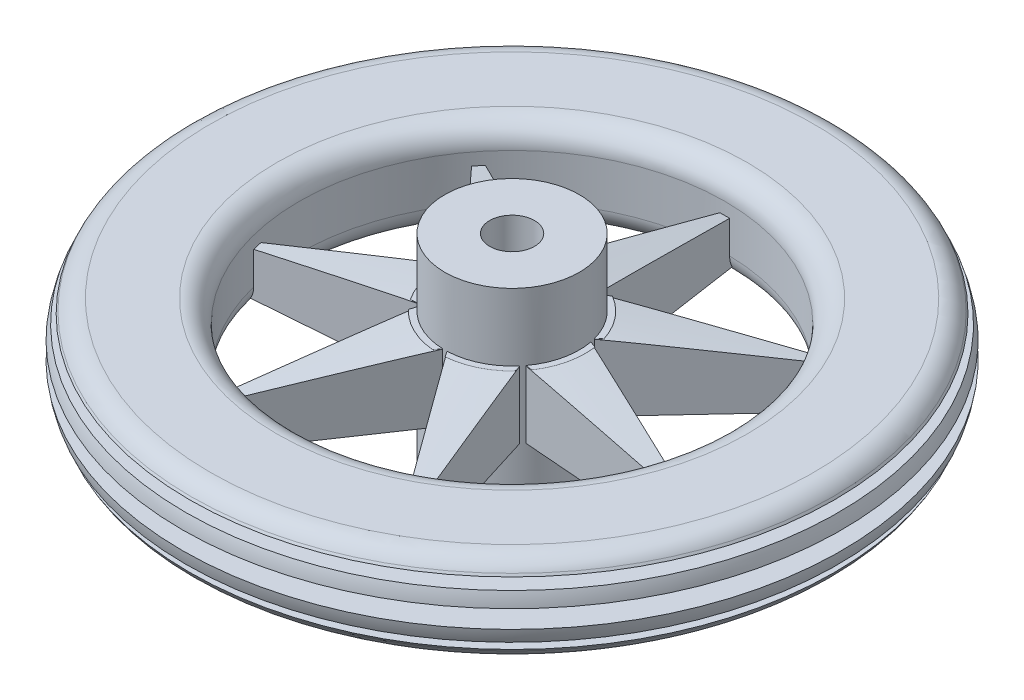
SolidWorks part; units mm, degrees
ref_plane "Front Plane" through (0, 0, 0) normal (0, 0, 1) x (1, 0, 0)
ref_plane "Top Plane" through (0, 0, 0) normal (0, 1, 0) x (1, 0, 0)
ref_plane "Right Plane" through (0, 0, 0) normal (1, 0, 0) x (0, 0, -1)
sketch "Sketch1" plane through (0, 0, 0) normal (0, 1, 0) x (1, 0, 0)
  circle A0 centre (0, 0) radius 50
  dimension "D1" = 100
sketch "Sketch2" plane through (0, 0, 0) normal (1, 0, 0) x (0, 0, -1)
  line L0 (50, 0) -> (-50, 0) construction
  line L1 (-58.6107, 0) -> (-80.5773, 0) construction
  line L2 (-69.791, 10) -> (-47.4303, 10)
  line L3 (-69.791, -10) -> (-47.4303, -10)
  line L4 (-47.4303, 10) -> (-47.4303, -10)
  line L5 (-73.4767, 2) -> (-59.6667, 2)
  line L6 (-59.6667, 2) -> (-59.6667, -2)
  line L7 (-59.6667, -2) -> (-73.4767, -2)
  line L8 (-71.8772, -7) -> (-59.6667, -7)
  line L9 (-59.6667, -7) -> (-59.6667, -5)
  line L10 (-59.6667, -5) -> (-72.7528, -5)
  line L11 (-59.6667, 7) -> (-59.6667, 5)
  line L12 (-59.6667, 5) -> (-72.7528, 5)
  line L13 (-71.8772, 7) -> (-59.6667, 7)
  line L14 (-58.6107, 0) -> (-58.6107, 15.4719) construction
  arc A0 (-69.791, 10) -> (-71.8772, 7) centre (-58.6107, 0) ccw
  arc A2 (-72.7528, 5) -> (-73.4767, 2) centre (-58.6107, 0) ccw
  arc A3 (-73.4767, -2) -> (-72.7528, -5) centre (-58.6107, 0) ccw
  arc A4 (-71.8772, -7) -> (-69.791, -10) centre (-58.6107, 0) ccw
  dimension "D1" = 30
  dimension "D2" = 10
  dimension "D3" = 10
  dimension "D4" = 4
  dimension "D5" = 2
  dimension "D6" = 2
  dimension "D7" = 5
  dimension "D8" = 20
sweep "Sweep1" add profiles "Sketch2" path "Sketch1"
sketch "Sketch3" plane through (0, 0, 0) normal (0, 1, 0) x (1, 0, 0)
  line L0 (37.7487, 28.7171) -> (14.507, 3.814)
  line L1 (6.9465, 13.2946) -> (36.397, 30.4121)
  line L2 (45.9879, -11.6083) -> (12.0269, -8.9641)
  line L3 (-6.0631, 13.72) -> (-1.084, 47.4179)
  line L4 (1.084, 47.4179) -> (6.0631, 13.72)
  line L5 (14.7252, 2.8581) -> (46.4703, -9.4947)
  line L6 (19.5973, -43.1924) -> (0.4902, -14.992)
  line L7 (11.4156, -9.7306) -> (21.5505, -42.2518)
  line L8 (-21.5505, -42.2518) -> (-11.4156, -9.7306)
  line L9 (-0.4902, -14.992) -> (-19.5973, -43.1924)
  line L10 (-46.4703, -9.4947) -> (-14.7252, 2.8581)
  line L11 (-12.0269, -8.9641) -> (-45.9879, -11.6083)
  line L12 (-36.397, 30.4121) -> (-6.9465, 13.2946)
  line L13 (-14.507, 3.814) -> (-37.7487, 28.7171)
  circle A0 centre (0, 0) radius 47.4303 construction
  arc A1 (1.084, 47.4179) -> (-1.084, 47.4179) centre (0, 0) ccw
  circle A2 centre (0, 0) radius 15
  arc A5 (37.7487, 28.7171) -> (36.397, 30.4121) centre (0, 0) ccw
  circle A6 centre (0, 0) radius 15
  arc A7 (45.9879, -11.6083) -> (46.4703, -9.4947) centre (0, 0) ccw
  circle A8 centre (0, 0) radius 15
  arc A9 (19.5973, -43.1924) -> (21.5505, -42.2518) centre (0, 0) ccw
  circle A10 centre (0, 0) radius 15
  arc A11 (-21.5505, -42.2518) -> (-19.5973, -43.1924) centre (0, 0) ccw
  circle A12 centre (0, 0) radius 15
  arc A13 (-46.4703, -9.4947) -> (-45.9879, -11.6083) centre (0, 0) ccw
  circle A14 centre (0, 0) radius 15
  arc A15 (-36.397, 30.4121) -> (-37.7487, 28.7171) centre (0, 0) ccw
  circle A16 centre (0, 0) radius 15
  point P41 (0, 0)
  dimension "D1" = 30
  dimension "D2" = 7
extrude "Boss-Extrude2" add sketch "Sketch3" along normal mid plane 15 contours L12 A15 L13 A2 | A2 L4 A1 L3 | L0 A5 L1 A2 | L2 A7 L5 A2 | L6 A9 L7 A2 | L8 A11 L9 A2 | L10 A13 L11 A2 region at (21.282, 0, -16.9718) region at (26.5382, 0, 6.0572) region at (0, 0, -27.2207) region at (11.8106, 0, 24.525) region at (-21.282, 0, -16.9718) region at (-11.8106, 0, 24.525) region at (-26.5382, 0, 6.0572)
sketch "Sketch4" plane through (0, 0, 0) normal (0, 1, 0) x (1, 0, 0)
  circle A0 centre (0, 0) radius 15
extrude "Boss-Extrude3" add sketch "Sketch4" along normal mid plane 45
sketch "Sketch7" plane through (0, 0, 0) normal (1, 0, 0) x (0, 0, -1)
  line L0 (0, 38.4643) -> (0, -41.56) construction
sketch "Sketch5" plane through (0, 22.5, 0) normal (0, 1, 0) x (1, 0, 0)
  circle A0 centre (0, 0) radius 5
  dimension "D1" = 10
extrude "Cut-Extrude1" cut sketch "Sketch5" against normal blind 53 and the other way blind 19
sketch "Sketch6" plane through (0, 0, 0) normal (1, 0, 0) x (0, 0, -1)
  line L0 (-47.4303, 2.2525) -> (-15, 7.4241)
  line L1 (-47.4303, -10) -> (-47.4303, 10) construction
  line L2 (-15, 22.5) -> (-15, -22.5) construction
  line L3 (-15, 7.4241) -> (-47.4303, 9.2525)
  line L4 (-47.4303, 9.2525) -> (-47.4303, 2.2525)
  dimension "D1" = 7
  dimension "D2" = 12.287
revolve "Cut-Revolve1" cut sketch "Sketch6" angle 360 about L0
fillet "Fillet1" radius 5 4 edges at (0, -10, 69.791) (0, 10, 69.791) (0, -10, 47.4303) (0, 10, 47.4303)
